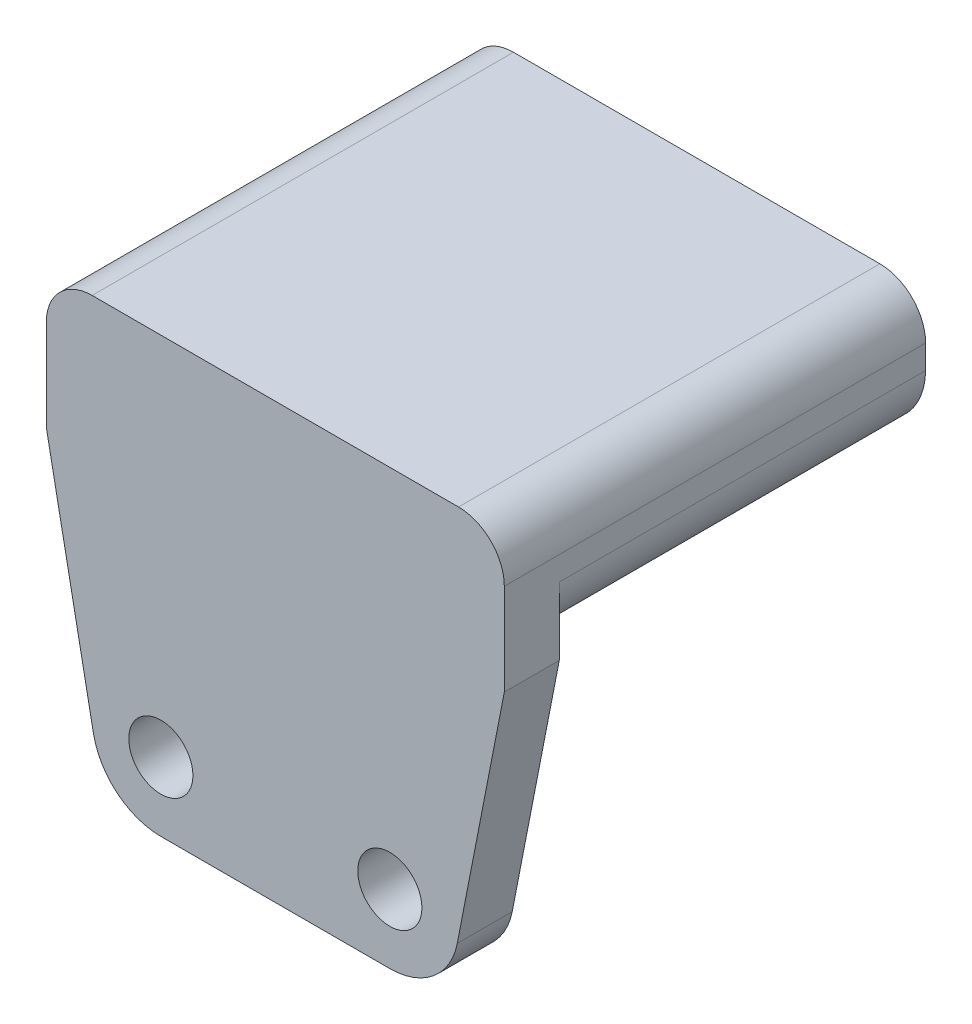
SolidWorks part; units mm, degrees
ref_plane "前视基准面" through (0, 0, 0) normal (0, 0, 1) x (1, 0, 0)
ref_plane "上视基准面" through (0, 0, 0) normal (0, 1, 0) x (1, 0, 0)
ref_plane "右视基准面" through (0, 0, 0) normal (1, 0, 0) x (0, 0, -1)
sketch "草图1" plane through (0, 0, 0) normal (0, 0, 1) x (1, 0, 0)
  line L0 (-12.5, 0) -> (12.5, 0) construction
  line L1 (0, 0) -> (0, 40) construction
  line L2 (-12.5, 0) -> (-20, 0) construction
  line L3 (-12.5, 0) -> (-12.5, -7.5) construction
  line L4 (-12.5, -7.5) -> (12.5, -7.5)
  line L8 (-25, 24.903) -> (-19.8612, -1.4362)
  line L10 (-25, 24.903) -> (-25, 34.903)
  line L11 (-20, 39.903) -> (20, 39.903)
  line L12 (25, 24.903) -> (25, 34.903)
  line L13 (-25, 24.903) -> (25, 39.903) construction
  line L14 (-25, 39.903) -> (25, 24.903) construction
  line L15 (-19.8612, -1.4362) -> (-12.5, 0) construction
  line L16 (25, 24.903) -> (19.8612, -1.4362)
  line L17 (-17.5, 24.903) -> (17.5, 24.903)
  circle A0 centre (-12.5, 0) radius 3.5
  circle A1 centre (12.5, 0) radius 3.5
  arc A6 (-19.8612, -1.4362) -> (-12.5, -7.5) centre (-12.5, 0) ccw
  arc A7 (12.5, -7.5) -> (19.8612, -1.4362) centre (12.5, 0) ccw
  arc A8 (17.5, 24.903) -> (25, 32.5) centre (17.5006, 32.403) ccw
  arc A9 (-17.5, 24.903) -> (-25, 32.403) centre (-17.5, 32.403) cw
  arc A10 (20, 39.903) -> (25, 34.903) centre (20, 34.903) cw
  arc A11 (-25, 34.903) -> (-20, 39.903) centre (-20, 34.903) cw
  point P4 (0, 0)
  point P19 (0, 32.403)
  point P25 (0, 24.903)
  dimension "D1" = 7
  dimension "D3" = 7
  dimension "D6" = 5
  dimension "D2" = 40
  dimension "D4" = 7.5
  dimension "D5" = 7.5
  dimension "D7" = 15
  dimension "D8" = 50
extrude "凸台-拉伸1" add sketch "草图1" along normal blind 6 contours L17 A9 L10 L8 A6 L4 A7 L16 L12 A8 A0 A1 | A11 L10 A9 L17 A8 L12 A10 L11 region at (-0.0001, 10.5074, 0) region at (0.0002, 32.5039, 0)
extrude "凸台-拉伸2" add sketch "草图1<6>" against normal blind 40 contours A11 L10 A9 L17 A8 L12 A10 L11 region at (0.0002, 32.5039, 0)
sketch "草图1<6>" plane through (0, 0, 0) normal (0, 0, 1) x (1, 0, 0) same geometry as "草图1"
